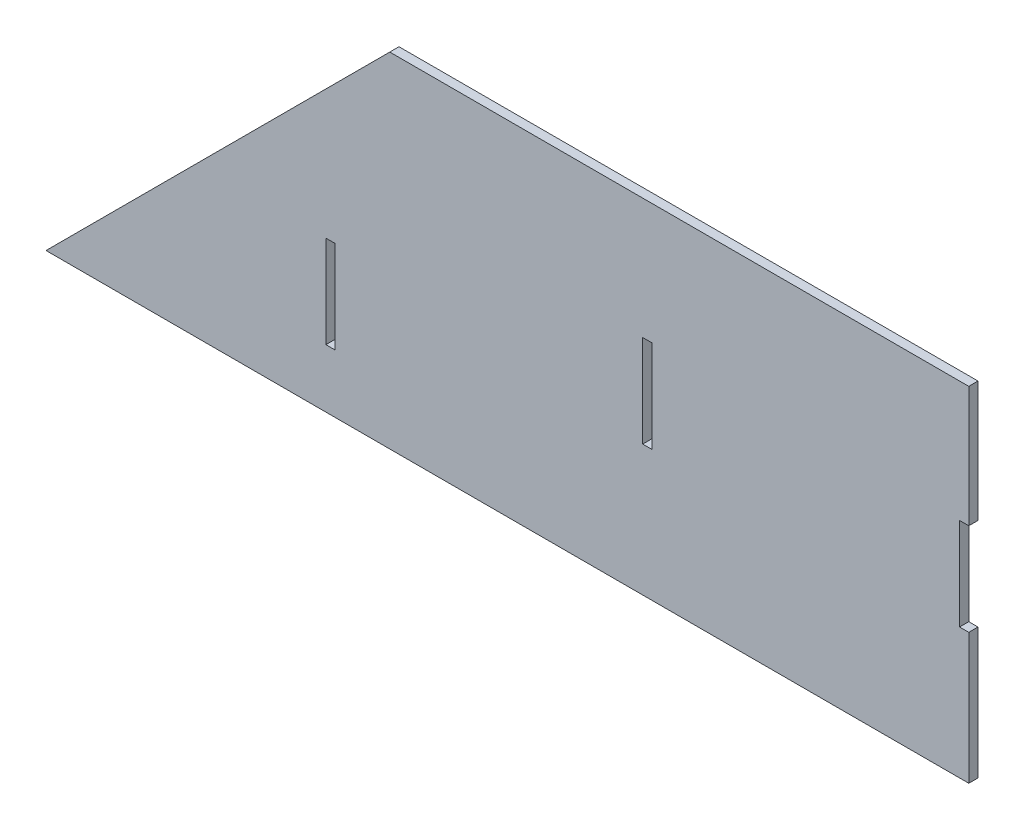
SolidWorks part; units mm, degrees
ref_plane "Front Plane" through (0, 0, 0) normal (0, 0, 1) x (1, 0, 0)
ref_plane "Top Plane" through (0, 0, 0) normal (0, 1, 0) x (1, 0, 0)
ref_plane "Right Plane" through (0, 0, 0) normal (1, 0, 0) x (0, 0, -1)
sketch "Sketch1" plane through (0, 0, 0) normal (0, 0, 1) x (1, 0, 0)
  line L21 (0, 0) -> (111.7616, 111.7616)
  line L22 (111.7616, 111.7616) -> (300, 111.7616)
  line L24 (300, 0) -> (0, 0)
  line L25 (300, 111.7616) -> (300, 72.5)
  line L26 (300, 72.5) -> (297, 72.5)
  line L27 (297, 72.5) -> (297, 42.5)
  line L28 (297, 42.5) -> (300, 42.5)
  line L29 (300, 42.5) -> (300, 0)
  line L30 (297, 57.5) -> (46.3855, 57.5) construction
  line L32 (197, 42.5) -> (194, 42.5)
  line L33 (197, 42.5) -> (197, 72.5)
  line L34 (197, 72.5) -> (194, 72.5)
  line L35 (194, 42.5) -> (194, 72.5)
  line L36 (197, 42.5) -> (194, 72.5) construction
  line L37 (197, 72.5) -> (194, 42.5) construction
  line L38 (94, 18.9921) -> (91, 18.9921)
  line L39 (94, 18.9921) -> (94, 48.9921)
  line L40 (94, 48.9921) -> (91, 48.9921)
  line L41 (91, 18.9921) -> (91, 48.9921)
  line L42 (94, 18.9921) -> (91, 48.9921) construction
  line L43 (94, 48.9921) -> (91, 18.9921) construction
  point P8 (195.5, 57.5)
  point P16 (291.0168, 42.5)
  point P17 (296.5828, 72.5)
  point P18 (92.5, 33.9921)
  point P23 (300.813, 72.5)
  dimension "D2" = 45
  dimension "D3" = 300
  dimension "D4" = 30
  dimension "D5" = 57.5
  dimension "D6" = 3
  dimension "D7" = 30
  dimension "D8" = 100
  dimension "D9" = 3
  dimension "D10" = 100
  dimension "D11" = 30
  dimension "D12" = 3
  dimension "D13" = 3
extrude "Boss-Extrude1" add sketch "Sketch1" along normal blind 3 contours L29 L28 L27 L26 L25 L22 L21 L24 L32 L35 L34 L33 L38 L41 L40 L39 region at (175.6116, 51.6365, 0)
